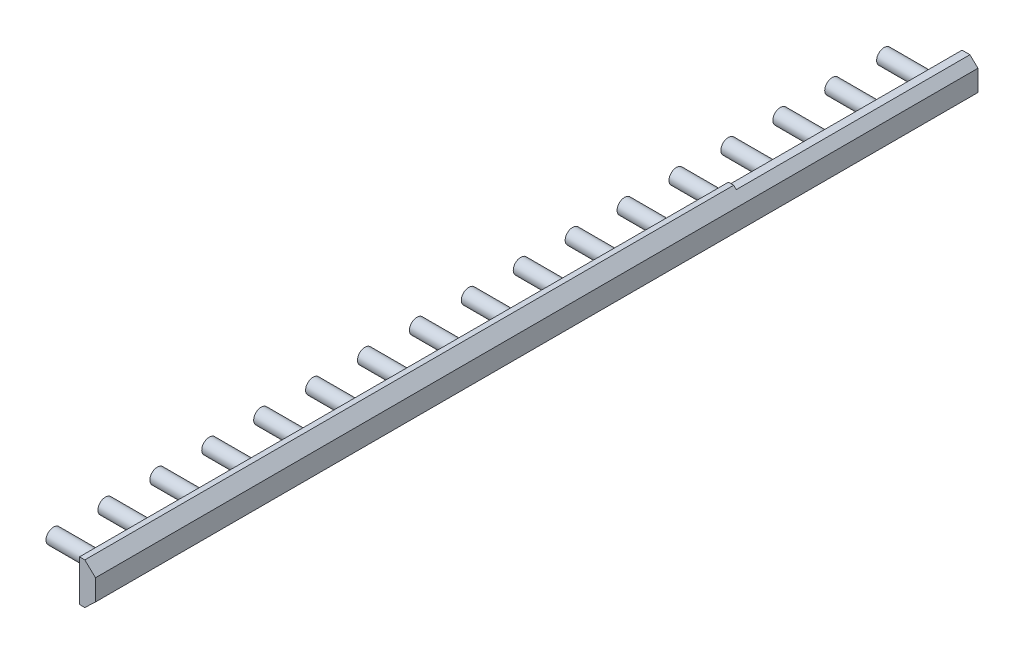
SolidWorks part; units mm, degrees
ref_plane "Front Plane" through (0, 0, 0) normal (0, 0, 1) x (1, 0, 0)
ref_plane "Top Plane" through (0, 0, 0) normal (0, 1, 0) x (1, 0, 0)
ref_plane "Right Plane" through (0, 0, 0) normal (1, 0, 0) x (0, 0, -1)
sketch "Sketch1" plane through (0, 0, 0) normal (0, 0, 1) x (1, 0, 0)
  line B0 (0, 7.95) -> (2.04, 7.95)
  line B1 (6.1524, 4.048) -> (6.1524, -4.048)
  line B2 (2.04, -7.95) -> (0, -7.95)
  line B3 (0, -7.95) -> (0, 7.95)
  line B4 (2.04, 7.95) -> (6.1524, 4.048)
  line B5 (6.1524, -4.048) -> (2.04, -7.95)
sketch_block_instance "Extrusion Profile-1"
sketch_block "Extrusion Profile" parameters "D1"=8.44, "D2"=2.6, "D3"=6, "D4"=16.7, "D6"=5.6686, "D7"=2.0404, "D8"=8.0963, "D9"=15.9, "D5"=2.4157
extrude "Boss-Extrude1" add sketch "Sketch1" along normal blind 340
sketch "Sketch2" plane through (0, 0, 0) normal (-1, 0, 0) x (0, 0, 1)
  circle A0 centre (10, 0) radius 2.9
  circle A1 centre (30, 0) radius 2.9
  circle A2 centre (50, 0) radius 2.9
  circle A3 centre (70, 0) radius 2.9
  circle A4 centre (90, 0) radius 2.9
  circle A5 centre (110, 0) radius 2.9
  circle A6 centre (130, 0) radius 2.9
  circle A7 centre (150, 0) radius 2.9
  circle A8 centre (170, 0) radius 2.9
  circle A9 centre (190, 0) radius 2.9
  circle A10 centre (210, 0) radius 2.9
  circle A11 centre (230, 0) radius 2.9
  circle A12 centre (250, 0) radius 2.9
  dimension "D2" = 5.8
  dimension "D1" = 10
  dimension "D4" = 20
  dimension "D3" = 13
extrude "Boss-Extrude2" add sketch "Sketch2" along normal blind 20
sketch "Sketch3" [suppressed] plane through (0, 0, 0) normal (-1, 0, 0) x (0, 0, 1)
  line L0 (190, 0) -> (210, 0) construction
  line L1 (200, 0) -> (200, 7.95) construction
  line L2 (260, 7.95) -> (0, 7.95) construction
  line L3 (200, 7.95) -> (200, 7)
  line L4 (200, 7) -> (100, 7)
  line L5 (100, 7) -> (100, 7.95)
  line L6 (100, 7.95) -> (200, 7.95)
  line L7 (90, 0) -> (110, 0) construction
  line L8 (100, 0) -> (100, 7) construction
  dimension "D1" = 7
extrude "Cut-Extrude1" [suppressed] cut sketch "Sketch3" against normal through all
chamfer "Chamfer1" [suppressed] distance 3 angle 45
fillet "Fillet1" [suppressed] radius 8
sketch "Sketch4" plane through (0, 0, 0) normal (-1, 0, 0) x (0, 0, 1)
  line L0 (250, 0) -> (230, 0) construction
  line L1 (250, 0) -> (270, 0) construction
  circle A0 centre (270, 0) radius 2.9
  circle A1 centre (250, 0) radius 2.9 construction
  circle A2 centre (290, 0) radius 2.9
  circle A3 centre (310, 0) radius 2.9
  circle A4 centre (330, 0) radius 2.9
  dimension "D2" = 20
  dimension "D1" = 4
extrude "Boss-Extrude3" add sketch "Sketch4" along normal blind 20
sketch "Sketch5" [suppressed] plane through (0, 0, 340) normal (0, 0, 1) x (1, 0, 0)
  line L5 (0, -7.95) -> (0, -20.95)
  line L6 (0, -20.95) -> (6.1524, -20.95)
  line L7 (6.1524, -20.95) -> (6.1524, -4.048)
  line L8 (0, -7.95) -> (2.04, -7.95) construction
  line L9 (0, -7.95) -> (2.04, -7.95)
  line L10 (2.04, -7.95) -> (6.1524, -4.048)
  line L11 (0, 7.95) -> (0, 14.75)
  line L12 (0, 14.75) -> (6.1524, 14.75)
  line L13 (6.1524, 14.75) -> (6.1524, 4.048)
  line L14 (2.04, 7.95) -> (0, 7.95) construction
  line L15 (0, 7.95) -> (2.04, 7.95)
  line L16 (2.04, 7.95) -> (6.1524, 4.048)
  dimension "D1" = 13
  dimension "D2" = 6.8
extrude "Boss-Extrude4" [suppressed] add sketch "Sketch5" against normal up to surface (340 mm away) up to face at (2.7308, 0, 0)
sketch "Sketch7" [suppressed] plane through (0, 0, 340) normal (0, 0, 1) x (1, 0, 0)
  line L0 (6.1524, -20.95) -> (6.1524, 14.75) construction
  line L1 (6.1524, -4.25) -> (0, -4.25)
  line L2 (6.1524, -4.25) -> (6.1524, 3.75)
  line L3 (6.1524, 3.75) -> (0, 3.75)
  line L4 (0, -4.25) -> (0, 3.75)
  line L5 (0, 14.75) -> (0, -20.95) construction
  line L6 (0, -0.25) -> (6.1524, -0.25)
  line L8 (6.1524, 14.75) -> (0, 14.75) construction
  line M7 (6.1524, -20.95) -> (6.1524, 14.75)
  line M9 (0, 14.75) -> (0, -20.95)
  dimension "D1" = 8
  dimension "D2" = 15
extrude "Boss-Extrude5" [suppressed] add sketch "Sketch7" along normal blind 6 contours L6 L2 L3 M9 | L6 L4 L1 M7
ref_plane "Plane1" [suppressed] through (0, 0, 170) normal (0, 0, 1) x (1, 0, 0)
mirror "Mirror1" [suppressed] about plane through (0, 0, 170) normal (0, 0, 1)
sketch "Sketch8" plane through (0, 0, 0) normal (-1, 0, 0) x (0, 0, 1)
  line L0 (0, 7) -> (90, 7)
  line L1 (0, 7.95) -> (0, -7.95) construction
  line L2 (90, 7) -> (90, 7.95)
  line L3 (340, 7.95) -> (0, 7.95) construction
  line L4 (90, 7.95) -> (0, 7.95)
  line L5 (0, 7.95) -> (0, 7)
  circle A0 centre (10, 0) radius 2.9 construction
  dimension "D1" = 7
  dimension "D2" = 90
extrude "Cut-Extrude2" cut sketch "Sketch8" against normal blind 5
